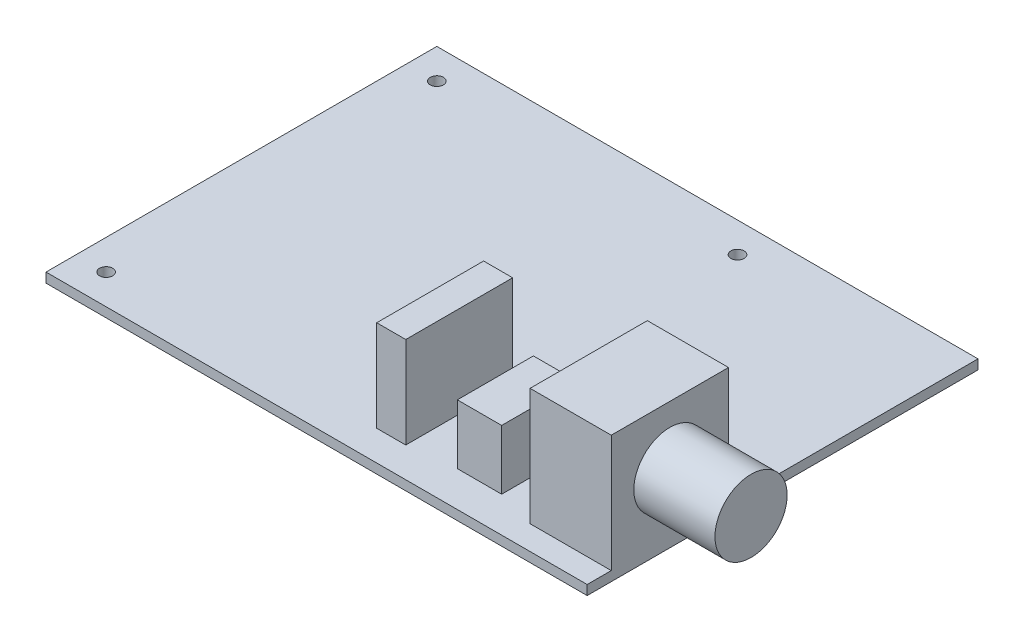
SolidWorks part; units mm, degrees
ref_plane "Front Plane" through (0, 0, 0) normal (0, 0, 1) x (1, 0, 0)
ref_plane "Top Plane" through (0, 0, 0) normal (0, 1, 0) x (1, 0, 0)
ref_plane "Right Plane" through (0, 0, 0) normal (1, 0, 0) x (0, 0, -1)
sketch "Sketch1" plane through (0, 0, 0) normal (0, 1, 0) x (1, 0, 0)
  line L1 (0, 0) -> (90, 0)
  line L2 (0, 0) -> (0, 65)
  line L3 (0, 65) -> (90, 65)
  line L4 (90, 0) -> (90, 65)
  circle A0 centre (5, 5) radius 1.1
  circle A1 centre (5, 60) radius 1.1
  circle A2 centre (55, 60) radius 1.1
  dimension "D3" = 2.2
  dimension "D6" = 5
  dimension "D7" = 5
  dimension "D9" = 5
  dimension "D1" = 65
  dimension "D2" = 90
  dimension "D4" = 5
  dimension "D5" = 5
  dimension "D8" = 55
extrude "Boss-Extrude1" add sketch "Sketch1" along normal blind 1.6
sketch "Sketch2" plane through (0, 0, 0) normal (0, -1, 0) x (1, 0, 0)
  line L0 (44.4, -51.5) -> (15, -63) construction
  line L1 (44.4, -63) -> (15, -63)
  line L2 (44.4, -63) -> (44.4, -51.5)
  line L3 (44.4, -51.5) -> (15, -51.5)
  line L4 (15, -63) -> (15, -51.5)
  line L5 (44.4, -63) -> (15, -51.5) construction
  line L6 (90, -65) -> (0, -65) construction
  line L7 (0, -65) -> (0, 0) construction
  line L8 (90, 0) -> (90, -65) construction
  line L9 (66, -63) -> (77.4, -63)
  line L10 (66, -63) -> (66, -51.5)
  line L11 (66, -51.5) -> (77.4, -51.5)
  line L12 (77.4, -63) -> (77.4, -51.5)
  point P4 (29.7, -57.25)
  dimension "D1" = 29.4
  dimension "D2" = 11.5
  dimension "D3" = 2
  dimension "D4" = 15
  dimension "D5" = 11.4
  dimension "D6" = 24
extrude "Cell and thermistor connectors" add sketch "Sketch2" along normal blind 9.25 thin thin type one direction reverse wall 1
sketch "Sketch3" plane through (0, 1.6, 0) normal (0, 1, 0) x (1, 0, 0)
  line L0 (90, 0) -> (90, 65) construction
  line L1 (90, 23.5071) -> (76.5, 23.5071)
  line L2 (90, 23.5071) -> (90, 4.0071)
  line L3 (90, 4.0071) -> (76.5, 4.0071)
  line L4 (76.5, 23.5071) -> (76.5, 4.0071)
  dimension "D1" = 13.5
  dimension "D2" = 19.5
extrude "Boss-Extrude2" add sketch "Sketch3" along normal blind 19.5
sketch "Sketch4" plane through (90, 0, 0) normal (1, 0, 0) x (0, 0, -1)
  line L0 (4.0071, 21.1) -> (23.5071, 21.1) construction
  line L1 (4.0071, 21.1) -> (4.0071, 1.6) construction
  circle A0 centre (13.7571, 11.35) radius 6
  point P2 (13.7571, 21.1)
  point P3 (4.0071, 11.35)
  dimension "D1" = 12
extrude "Boss-Extrude3" add sketch "Sketch4" along normal blind 13.5
sketch "Sketch5" plane through (0, 1.6, 0) normal (0, 1, 0) x (1, 0, 0)
  line L0 (0, 65) -> (0, 0) construction
  line L1 (54.83, 22.78) -> (50, 22.78)
  line L2 (54.83, 22.78) -> (54.83, 5)
  line L3 (54.83, 5) -> (50, 5)
  line L4 (50, 22.78) -> (50, 5)
  line L5 (0, 0) -> (90, 0) construction
  dimension "D1" = 17.78
  dimension "D2" = 4.83
  dimension "D3" = 50
  dimension "D4" = 5
extrude "JTAG header" add sketch "Sketch5" along normal blind 15.2
sketch "Sketch6" plane through (0, 1.6, 0) normal (0, 1, 0) x (1, 0, 0)
  line L1 (69.8885, 18.5411) -> (62.5185, 18.5411)
  line L2 (69.8885, 18.5411) -> (69.8885, 5.8911)
  line L3 (69.8885, 5.8911) -> (62.5185, 5.8911)
  line L4 (62.5185, 18.5411) -> (62.5185, 5.8911)
  dimension "D1" = 12.65
  dimension "D2" = 7.37
extrude "Aux. CAN header" add sketch "Sketch6" along normal blind 9.91
equation "\"D1@Sketch5\"=7*2.54"
equation "\"D1@JTAG header\"=11.4+3.8"
